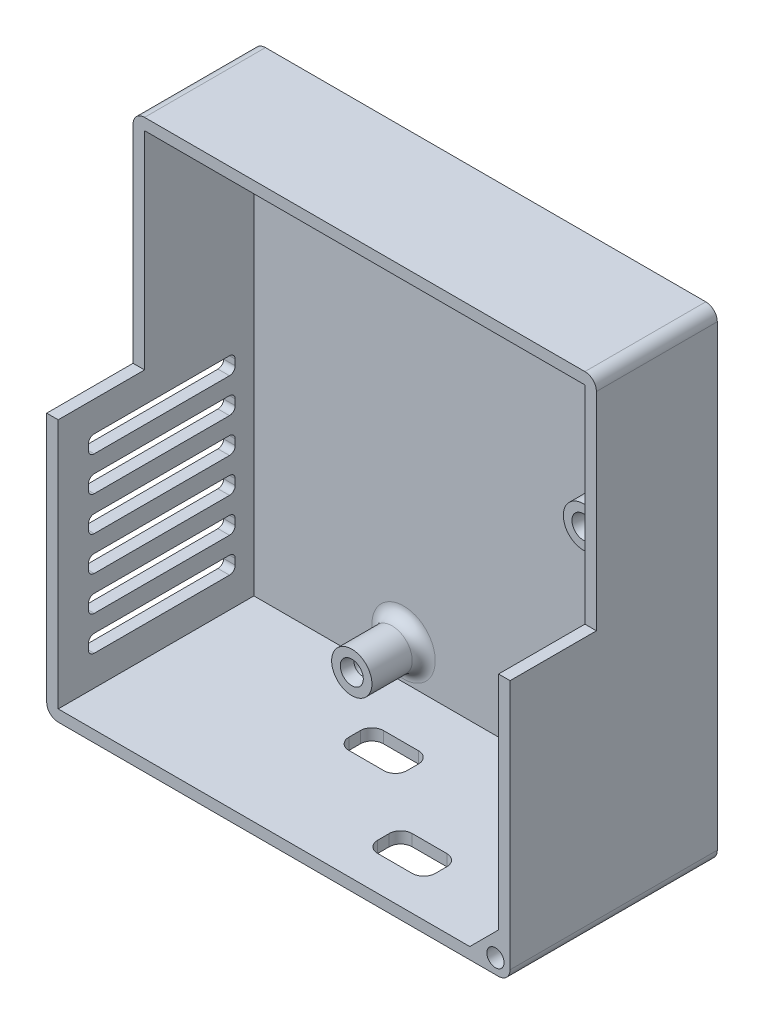
SolidWorks part; units mm, degrees
ref_plane "Front Plane" through (0, 0, 0) normal (1, 0, 0) x (0, 1, 0)
ref_plane "Top Plane" through (0, 0, 0) normal (0, 0, 1) x (0, 1, 0)
ref_plane "Right Plane" through (0, 0, 0) normal (0, 1, 0) x (-1, 0, 0)
sketch "Sketch1" plane through (0, 0, 0) normal (0, 0, 1) x (0, 1, 0)
  line L0 (-39.75, 38.25) -> (39.75, 38.25)
  line L1 (-41.75, 40.25) -> (41.75, 40.25)
  line L2 (-41.75, 40.25) -> (-41.75, -40.25)
  line L3 (-41.75, -40.25) -> (41.75, -40.25)
  line L4 (41.75, 40.25) -> (41.75, -40.25)
  line L5 (-41.75, 40.25) -> (41.75, -40.25) construction
  line L6 (-41.75, -40.25) -> (41.75, 40.25) construction
  line L7 (39.75, 38.25) -> (39.75, -38.25)
  line L8 (-39.75, -38.25) -> (39.75, -38.25)
  line L9 (-39.75, 38.25) -> (-39.75, -38.25)
  circle A0 centre (-33.75, 12.25) radius 3.5
  circle A1 centre (33.75, 12.25) radius 3.5
  circle A2 centre (8.25, -28) radius 3.5
  circle A3 centre (-33.75, 12.25) radius 1.5
  circle A4 centre (33.75, 12.25) radius 1.5
  circle A5 centre (8.25, -28) radius 1.5
  point P0 (0, 0)
  dimension "D4" = 3
  dimension "D5" = 7
  dimension "D6" = 3
  dimension "D7" = 7
  dimension "D8" = 3
  dimension "D9" = 7
  dimension "D1" = 83.5
  dimension "D2" = 80.5
  dimension "D10" = 6
  dimension "D11" = 26
  dimension "D12" = 6
  dimension "D13" = 26
  dimension "D14" = 42
  dimension "D15" = 40.25
  dimension "D3" = 2
extrude "Boss-Extrude1" add sketch "Sketch1" against normal blind 2 contours L4 L3 L2 L1
extrude "Boss-Extrude2" add sketch "Sketch1<3>" along normal blind 9 contours L4 L1 L2 L3 L9 L0 L7 L8 | A2 A5 | A1 A4 | A0 A3 region at (-39.0902, 0, 0) region at (-12.25, -37.151, 0) region at (-12.25, 30.349, 0) region at (28, 4.849, 0)
sketch "Sketch1<3>" plane through (0, 0, 0) normal (0, 0, 1) x (0, 1, 0) same geometry as "Sketch1"
chamfer "Chamfer1" distance 0.5 angle 75 3 edges at (-10.75, -33.75, 9) (29.5, 8.25, 9) (-10.75, 33.75, 9) first distance on face at (-10.75, -33.75, 9) first distance on face at (29.5, 8.25, 9) first distance on face at (-10.75, 33.75, 9)
sketch "Sketch4" plane through (0, 0, 9) normal (0, 0, 1) x (1, 0, 0)
  line L1 (-40.25, 41.75) -> (40.25, 41.75)
  line L2 (-40.25, 41.75) -> (-40.25, -41.75)
  line L3 (-40.25, -41.75) -> (40.25, -41.75)
  line L4 (40.25, 41.75) -> (40.25, -41.75)
  line L5 (-38.25, -39.75) -> (38.25, -39.75)
  line L6 (-38.25, -39.75) -> (-38.25, 39.75)
  line L7 (-38.25, 39.75) -> (38.25, 39.75)
  line L8 (38.25, -39.75) -> (38.25, 39.75)
extrude "Boss-Extrude3" add sketch "Sketch4" along normal blind 25
sketch "Sketch5" plane through (0, -41.75, 0) normal (0, -1, 0) x (1, 0, 0)
  line L0 (-40.25, -2) -> (-40.25, 34) construction
  line L1 (11.25, 28) -> (17.25, 28)
  line L2 (9.25, 26) -> (9.25, 24)
  line L3 (11.25, 22) -> (17.25, 22)
  line L4 (19.25, 26) -> (19.25, 24)
  line L5 (9.25, 28) -> (19.25, 22) construction
  line L6 (9.25, 22) -> (19.25, 28) construction
  line L7 (-40.25, -2) -> (40.25, -2) construction
  line L8 (-6.75, 15) -> (-0.67, 15)
  line L9 (-8.75, 13) -> (-8.75, 11)
  line L10 (-6.75, 9) -> (-0.67, 9)
  line L11 (1.33, 13) -> (1.33, 11)
  line L12 (-8.75, 15) -> (1.33, 9) construction
  line L13 (-8.75, 9) -> (1.33, 15) construction
  arc A0 (11.25, 28) -> (9.25, 26) centre (11.25, 26) ccw
  arc A1 (19.25, 26) -> (17.25, 28) centre (17.25, 26) ccw
  arc A2 (19.25, 24) -> (17.25, 22) centre (17.25, 24) cw
  arc A3 (9.25, 24) -> (11.25, 22) centre (11.25, 24) ccw
  arc A4 (-6.75, 15) -> (-8.75, 13) centre (-6.75, 13) ccw
  arc A5 (-0.67, 15) -> (1.33, 13) centre (-0.67, 13) cw
  arc A6 (1.33, 11) -> (-0.67, 9) centre (-0.67, 11) cw
  arc A7 (-8.75, 11) -> (-6.75, 9) centre (-6.75, 11) ccw
  point P0 (14.25, 25)
  point P7 (-3.71, 12)
  dimension "D9" = 2
  dimension "D10" = 2
  dimension "D11" = 2
  dimension "D12" = 2
  dimension "D13" = 2
  dimension "D14" = 2
  dimension "D15" = 2
  dimension "D16" = 2
  dimension "D1" = 49.5
  dimension "D2" = 31.5
  dimension "D3" = 10.08
  dimension "D4" = 11
  dimension "D5" = 6
  dimension "D6" = 24
  dimension "D7" = 6
  dimension "D8" = 10
extrude "Cut-Extrude1" cut sketch "Sketch5" against normal blind 16
fillet "Fillet1" radius 2 1 edges at (40.25, -41.75, 16)
fillet "Fillet2" radius 2 1 edges at (-40.25, -41.75, 16)
fillet "Fillet3" radius 2 1 edges at (40.25, 41.75, 16)
fillet "Fillet4" radius 2 1 edges at (-40.25, 41.75, 16)
fillet "Fillet5" radius 2 1 edges at (24.5, 8.25, 0)
fillet "Fillet6" radius 2 1 edges at (-15.75, -33.75, 0)
fillet "Fillet7" radius 2 1 edges at (-15.75, 33.75, 0)
sketch "Sketch6" plane through (-40.25, 0, 0) normal (-1, 0, 0) x (0, -1, 0)
  line L0 (-39.75, 16) -> (39.75, 16) construction
  line L1 (33.5, 3.25) -> (32.5, 3.25)
  line L2 (34.5, 4.25) -> (34.5, 27.75)
  line L3 (33.5, 28.75) -> (32.5, 28.75)
  line L4 (31.5, 4.25) -> (31.5, 27.75)
  line L5 (34.5, 3.25) -> (31.5, 28.75) construction
  line L6 (34.5, 28.75) -> (31.5, 3.25) construction
  line L7 (-39.75, 34) -> (-39.75, -2) construction
  line L8 (39.75, -2) -> (39.75, 34) construction
  line L10 (39.75, -2) -> (-39.75, -2) construction
  line L56 (28.5, 4.25) -> (28.5, 27.75)
  line L57 (27.5, 3.25) -> (26.5, 3.25)
  line L58 (25.5, 4.25) -> (25.5, 27.75)
  line L59 (27.5, 28.75) -> (26.5, 28.75)
  line L60 (22.5, 4.25) -> (22.5, 27.75)
  line L61 (21.5, 3.25) -> (20.5, 3.25)
  line L62 (19.5, 4.25) -> (19.5, 27.75)
  line L63 (21.5, 28.75) -> (20.5, 28.75)
  line L64 (16.5, 4.25) -> (16.5, 27.75)
  line L65 (15.5, 3.25) -> (14.5, 3.25)
  line L66 (13.5, 4.25) -> (13.5, 27.75)
  line L67 (15.5, 28.75) -> (14.5, 28.75)
  line L68 (10.5, 4.25) -> (10.5, 27.75)
  line L69 (9.5, 3.25) -> (8.5, 3.25)
  line L70 (7.5, 4.25) -> (7.5, 27.75)
  line L71 (9.5, 28.75) -> (8.5, 28.75)
  line L72 (4.5, 4.25) -> (4.5, 27.75)
  line L73 (3.5, 3.25) -> (2.5, 3.25)
  line L74 (1.5, 4.25) -> (1.5, 27.75)
  line L75 (3.5, 28.75) -> (2.5, 28.75)
  line L100 (-1.5, 4.25) -> (-1.5, 27.75) [skipped]
  line L101 (-2.5, 3.25) -> (-3.5, 3.25) [skipped]
  line L102 (-4.5, 4.25) -> (-4.5, 27.75) [skipped]
  line L103 (-2.5, 28.75) -> (-3.5, 28.75) [skipped]
  line L104 (-7.5, 4.25) -> (-7.5, 27.75) [skipped]
  line L105 (-8.5, 3.25) -> (-9.5, 3.25) [skipped]
  line L106 (-10.5, 4.25) -> (-10.5, 27.75) [skipped]
  line L107 (-8.5, 28.75) -> (-9.5, 28.75) [skipped]
  line L108 (-13.5, 4.25) -> (-13.5, 27.75) [skipped]
  line L109 (-14.5, 3.25) -> (-15.5, 3.25) [skipped]
  line L110 (-16.5, 4.25) -> (-16.5, 27.75) [skipped]
  line L111 (-14.5, 28.75) -> (-15.5, 28.75) [skipped]
  line L112 (-19.5, 4.25) -> (-19.5, 27.75) [skipped]
  line L113 (-20.5, 3.25) -> (-21.5, 3.25) [skipped]
  line L114 (-22.5, 4.25) -> (-22.5, 27.75) [skipped]
  line L115 (-20.5, 28.75) -> (-21.5, 28.75) [skipped]
  line L116 (-25.5, 4.25) -> (-25.5, 27.75) [skipped]
  line L117 (-26.5, 3.25) -> (-27.5, 3.25) [skipped]
  line L118 (-28.5, 4.25) -> (-28.5, 27.75) [skipped]
  line L119 (-26.5, 28.75) -> (-27.5, 28.75) [skipped]
  line L120 (-31.5, 4.25) -> (-31.5, 27.75) [skipped]
  line L121 (-32.5, 3.25) -> (-33.5, 3.25) [skipped]
  line L122 (-32.5, 28.75) -> (-33.5, 28.75) [skipped]
  line L123 (-34.5, 4.25) -> (-34.5, 27.75) [skipped]
  arc A0 (34.5, 27.75) -> (33.5, 28.75) centre (33.5, 27.75) ccw
  arc A1 (32.5, 28.75) -> (31.5, 27.75) centre (32.5, 27.75) ccw
  arc A2 (34.5, 4.25) -> (33.5, 3.25) centre (33.5, 4.25) cw
  arc A3 (31.5, 4.25) -> (32.5, 3.25) centre (32.5, 4.25) ccw
  arc A4 (28.5, 4.25) -> (27.5, 3.25) centre (27.5, 4.25) cw
  arc A5 (28.5, 27.75) -> (27.5, 28.75) centre (27.5, 27.75) ccw
  arc A6 (25.5, 4.25) -> (26.5, 3.25) centre (26.5, 4.25) ccw
  arc A7 (26.5, 28.75) -> (25.5, 27.75) centre (26.5, 27.75) ccw
  arc A8 (22.5, 4.25) -> (21.5, 3.25) centre (21.5, 4.25) cw
  arc A9 (22.5, 27.75) -> (21.5, 28.75) centre (21.5, 27.75) ccw
  arc A10 (19.5, 4.25) -> (20.5, 3.25) centre (20.5, 4.25) ccw
  arc A11 (20.5, 28.75) -> (19.5, 27.75) centre (20.5, 27.75) ccw
  arc A12 (16.5, 4.25) -> (15.5, 3.25) centre (15.5, 4.25) cw
  arc A13 (16.5, 27.75) -> (15.5, 28.75) centre (15.5, 27.75) ccw
  arc A14 (13.5, 4.25) -> (14.5, 3.25) centre (14.5, 4.25) ccw
  arc A15 (14.5, 28.75) -> (13.5, 27.75) centre (14.5, 27.75) ccw
  arc A16 (10.5, 4.25) -> (9.5, 3.25) centre (9.5, 4.25) cw
  arc A17 (10.5, 27.75) -> (9.5, 28.75) centre (9.5, 27.75) ccw
  arc A18 (7.5, 4.25) -> (8.5, 3.25) centre (8.5, 4.25) ccw
  arc A19 (8.5, 28.75) -> (7.5, 27.75) centre (8.5, 27.75) ccw
  arc A20 (4.5, 4.25) -> (3.5, 3.25) centre (3.5, 4.25) cw
  arc A21 (4.5, 27.75) -> (3.5, 28.75) centre (3.5, 27.75) ccw
  arc A22 (1.5, 4.25) -> (2.5, 3.25) centre (2.5, 4.25) ccw
  arc A23 (2.5, 28.75) -> (1.5, 27.75) centre (2.5, 27.75) ccw
  arc A48 (-1.5, 4.25) -> (-2.5, 3.25) centre (-2.5, 4.25) cw [skipped]
  arc A49 (-1.5, 27.75) -> (-2.5, 28.75) centre (-2.5, 27.75) ccw [skipped]
  arc A50 (-4.5, 4.25) -> (-3.5, 3.25) centre (-3.5, 4.25) ccw [skipped]
  arc A51 (-3.5, 28.75) -> (-4.5, 27.75) centre (-3.5, 27.75) ccw [skipped]
  arc A52 (-7.5, 4.25) -> (-8.5, 3.25) centre (-8.5, 4.25) cw [skipped]
  arc A53 (-7.5, 27.75) -> (-8.5, 28.75) centre (-8.5, 27.75) ccw [skipped]
  arc A54 (-10.5, 4.25) -> (-9.5, 3.25) centre (-9.5, 4.25) ccw [skipped]
  arc A55 (-9.5, 28.75) -> (-10.5, 27.75) centre (-9.5, 27.75) ccw [skipped]
  arc A56 (-13.5, 4.25) -> (-14.5, 3.25) centre (-14.5, 4.25) cw [skipped]
  arc A57 (-13.5, 27.75) -> (-14.5, 28.75) centre (-14.5, 27.75) ccw [skipped]
  arc A58 (-16.5, 4.25) -> (-15.5, 3.25) centre (-15.5, 4.25) ccw [skipped]
  arc A59 (-15.5, 28.75) -> (-16.5, 27.75) centre (-15.5, 27.75) ccw [skipped]
  arc A60 (-19.5, 4.25) -> (-20.5, 3.25) centre (-20.5, 4.25) cw [skipped]
  arc A61 (-19.5, 27.75) -> (-20.5, 28.75) centre (-20.5, 27.75) ccw [skipped]
  arc A62 (-22.5, 4.25) -> (-21.5, 3.25) centre (-21.5, 4.25) ccw [skipped]
  arc A63 (-21.5, 28.75) -> (-22.5, 27.75) centre (-21.5, 27.75) ccw [skipped]
  arc A64 (-25.5, 4.25) -> (-26.5, 3.25) centre (-26.5, 4.25) cw [skipped]
  arc A65 (-25.5, 27.75) -> (-26.5, 28.75) centre (-26.5, 27.75) ccw [skipped]
  arc A66 (-28.5, 4.25) -> (-27.5, 3.25) centre (-27.5, 4.25) ccw [skipped]
  arc A67 (-27.5, 28.75) -> (-28.5, 27.75) centre (-27.5, 27.75) ccw [skipped]
  arc A68 (-31.5, 4.25) -> (-32.5, 3.25) centre (-32.5, 4.25) cw [skipped]
  arc A69 (-31.5, 27.75) -> (-32.5, 28.75) centre (-32.5, 27.75) ccw [skipped]
  arc A70 (-33.5, 28.75) -> (-34.5, 27.75) centre (-33.5, 27.75) ccw [skipped]
  arc A71 (-34.5, 4.25) -> (-33.5, 3.25) centre (-33.5, 4.25) ccw [skipped]
  point P0 (33, 16)
  dimension "D5" = 1
  dimension "D6" = 1
  dimension "D7" = 1
  dimension "D8" = 1
  dimension "D1" = 5.25
  dimension "D2" = 3
  dimension "D3" = 5.25
  dimension "D4" = 12
extrude "Cut-Extrude2" cut sketch "Sketch6" against normal blind 10
ref_plane "Plane1" through (-50.25, 0, 0) normal (-1, 0, 0) x (0, 0, 1)
sketch "Sketch9" plane through (-40.25, 0, 0) normal (-1, 0, 0) x (0, 0, 1)
  line L0 (34, 39.75) -> (34, -39.75) construction
  line L5 (34, 41.75) -> (19, 41.75)
  line L6 (34, 41.75) -> (34, 3.75)
  line L7 (34, 3.75) -> (19, 3.75)
  line L9 (19, 41.75) -> (19, 3.75)
  line L10 (34, 41.75) -> (19, 3.75) construction
  line L12 (34, 3.75) -> (19, 41.75) construction
  line L13 (-2, 41.75) -> (34, 41.75) construction
  line L14 (27.75, -1.5) -> (4.25, -1.5) construction
  point P0 (26.5, 22.75)
  dimension "D1" = 5.25
  dimension "D2" = 15
extrude "Cut-Extrude3" cut sketch "Sketch9" against normal blind 81
sketch "Sketch10" plane through (0, 0, 0) normal (0, 0, 1) x (1, 0, 0)
  line L0 (33.25, -39.75) -> (38.25, -34.75)
  line L1 (-38.25, -39.75) -> (38.25, -39.75) construction
  line L2 (38.25, -39.75) -> (38.25, 39.75) construction
  line L3 (33.25, -39.75) -> (38.25, -39.75)
  line L4 (38.25, -39.75) -> (38.25, -34.75)
  dimension "D1" = 5
  dimension "D2" = 5
extrude "Boss-Extrude4" add sketch "Sketch10" along normal blind 34
sketch "Sketch11" plane through (0, 0, 34) normal (0, 0, 1) x (1, 0, 0)
  line L0 (35.75, -37.25) -> (39.6642, -41.1642) construction
  line L1 (38.25, -34.75) -> (33.25, -39.75) construction
  circle A0 centre (37.7071, -39.2071) radius 1.5
  arc A1 (38.25, -41.75) -> (40.25, -39.75) centre (38.25, -39.75) ccw construction
  point P9 (0, 0)
  point P10 (37.7071, -39.2071)
  dimension "D1" = 3
extrude "Cut-Extrude4" cut sketch "Sketch11" against normal blind 10
